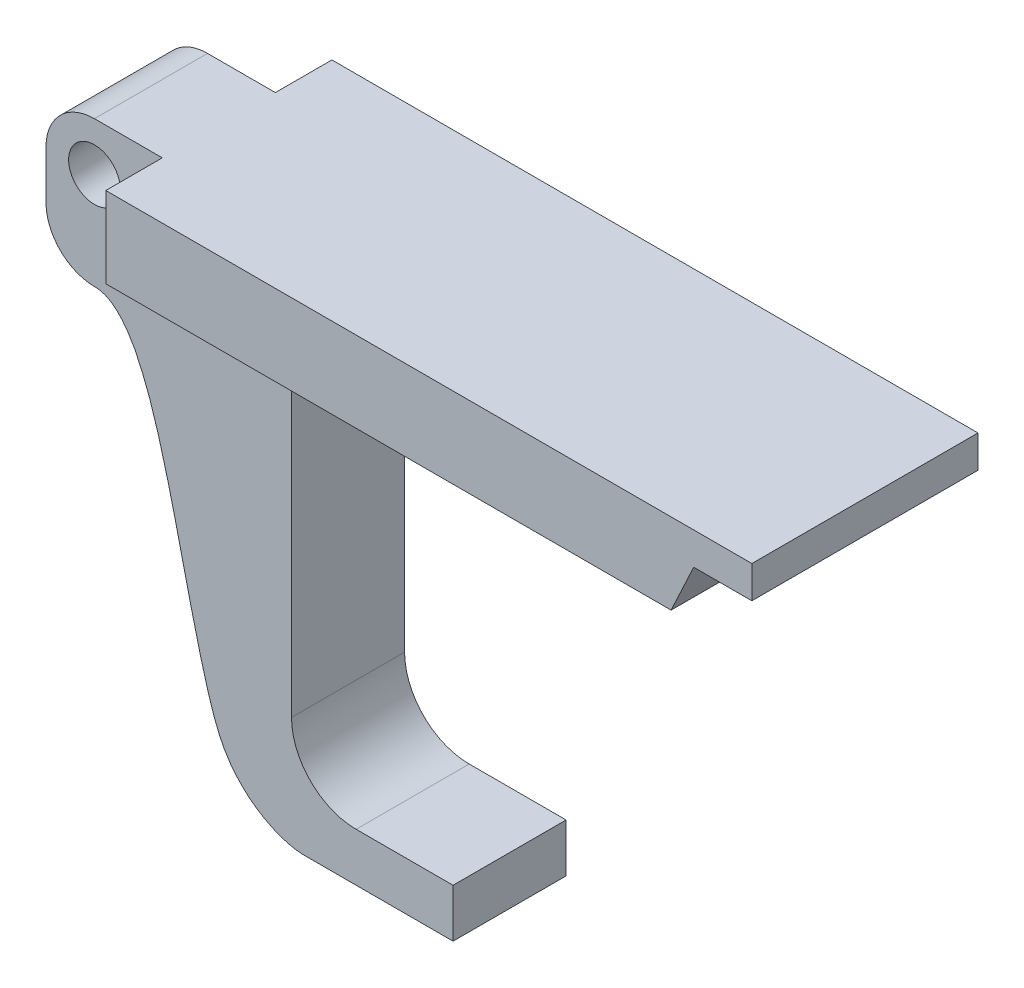
SolidWorks part; units mm, degrees
ref_plane "Ebene vorne" through (0, 0, 0) normal (0, 0, 1) x (1, 0, 0)
ref_plane "Ebene oben" through (0, 0, 0) normal (0, 1, 0) x (1, 0, 0)
ref_plane "Ebene rechts" through (0, 0, 0) normal (1, 0, 0) x (0, 0, -1)
sketch "Sketch1" plane through (0, 0, 0) normal (0, 1, 0) x (1, 0, 0)
  line L0 (-20, -7) -> (-20, -3.5)
  line L1 (-20, -7) -> (20, -7)
  line L2 (-20, 7) -> (20, 7)
  line L3 (20, -7) -> (20, 7)
  line L4 (-20, -7) -> (20, 7) construction
  line L5 (-20, 7) -> (20, -7) construction
  line L6 (-20, 3.5) -> (-20, 7)
  line L7 (-20, -3.5) -> (-27.2, -3.5)
  line L9 (-20, 3.5) -> (-27.2, 3.5)
  line L10 (-27.2, -3.5) -> (-27.2, 3.5)
  point P1 (0, 0)
  dimension "D1" = 14
  dimension "D2" = 40
  dimension "D3" = 7.2
  dimension "D4" = 7
extrude "Boss-Extrude1" add sketch "Sketch1" along normal blind 5
sketch "Sketch16" plane through (0, 0, 0) normal (0, -1, 0) x (1, 0, 0)
  line L1 (-20, 3.5) -> (-27.2, 3.5)
  line L2 (-20, 3.5) -> (-20, -3.5)
  line L3 (-20, -3.5) -> (-27.2, -3.5)
  line L4 (-27.2, 3.5) -> (-27.2, -3.5)
extrude "Boss-Extrude3" add sketch "Sketch16" along normal blind 4
sketch "Sketch17" plane through (0, 0, -3.5) normal (0, 0, -1) x (-1, 0, 0)
  line L0 (20, 5) -> (27.2, 5) construction
  line L1 (27.2, 5) -> (27.2, -4) construction
  circle A0 centre (24.2, 2) radius 1.6
  dimension "D1" = 3.2
  dimension "D2" = 3
  dimension "D3" = 3
extrude "Cut-Extrude4" cut sketch "Sketch17" against normal up to next
fillet "Fillet4" radius 3 2 edges at (-27.2, -4, 0) (-27.2, 5, 0)
sketch "Sketch18" plane through (0, 0, -3.5) normal (0, 0, -1) x (-1, 0, 0)
  line L1 (12, -21) -> (12, 0)
  line L2 (-20, 0) -> (20, 0) construction
  line L3 (12, 0) -> (20, 0)
  line L5 (2, -28) -> (10.9538, -28)
  line L6 (2, -28) -> (2, -25)
  line L7 (2, -25) -> (8, -25)
  line L10 (26.8692, -4) -> (21.5308, -4) construction
  line L11 (20, 0) -> (20, -4)
  line L12 (20, -4) -> (24.2, -4)
  arc A0 (8, -25) -> (12, -21) centre (8, -21) ccw
  spline S0 degree 3 poles (10.9538, -28) (12.5005, -28.089) (15.746, -26.6307) (19.1654, -16.2215) (20.6164, -4) (24.2, -4) knots 0 0 0 0 0.247683 0.347683 1 1 1 1
  point P15 (12, -25)
  dimension "D3" = 4
  dimension "D1" = 25
  dimension "D2" = 3
  dimension "D4" = 10
  dimension "D5" = 8
extrude "Boss-Extrude4" add sketch "Sketch18" against normal up to surface (7 mm away) up to face at (-25.8, 2, 3.5)
sketch "Sketch15" plane through (0, 0, 0) normal (0, -1, 0) x (1, 0, 0)
  line L0 (1, 0) -> (3, 0) construction
  line L1 (1, 3.5) -> (3, 3.5)
  line L2 (1, -3.5) -> (3, -3.5)
  line L7 (-2, 3.5) -> (-10.9538, 3.5)
  line L8 (-10.9538, 3.5) -> (-10.9538, -3.5)
  line L9 (-10.9538, -3.5) -> (-2, -3.5)
  line L10 (-2, -3.5) -> (-2, 3.5)
  line L11 (-2, 3.5) -> (-10.9538, 3.5) construction
  line L12 (-10.9538, 3.5) -> (-10.9538, -3.5) construction
  line L13 (-10.9538, -3.5) -> (-2, -3.5) construction
  line L14 (-2, -3.5) -> (-2, 3.5) construction
  arc A0 (1, 3.5) -> (1, -3.5) centre (1, 0) ccw
  arc A1 (3, -3.5) -> (3, 3.5) centre (3, 0) ccw
  point P3 (2, 0)
  dimension "D1" = 7
  dimension "D2" = 2
  dimension "D3" = 0
  dimension "D4" = 4
extrude "Cut-Extrude3" [suppressed] cut sketch "Sketch15" against normal up to next
fillet "Fillet5" radius 1 3 edges at (-16, 0, 3.5) (-12, 0, 0) (-16, 0, -3.5)
sketch "Sketch19" plane through (0, 0, 0) normal (0, -1, 0) x (1, 0, 0)
  line L0 (-20, 7) -> (20, 7) construction
  line L1 (15, 7) -> (20, 7)
  line L2 (15, 7) -> (15, -7)
  line L3 (15, -7) -> (20, -7)
  line L4 (20, 7) -> (20, -7)
  dimension "D1" = 5
extrude "Cut-Extrude5" cut sketch "Sketch19" against normal blind 3
chamfer "Chamfer1" distance 3 angle 25 1 edges at (15, 3, 0) first distance on face at (15, 1.5, 0)
